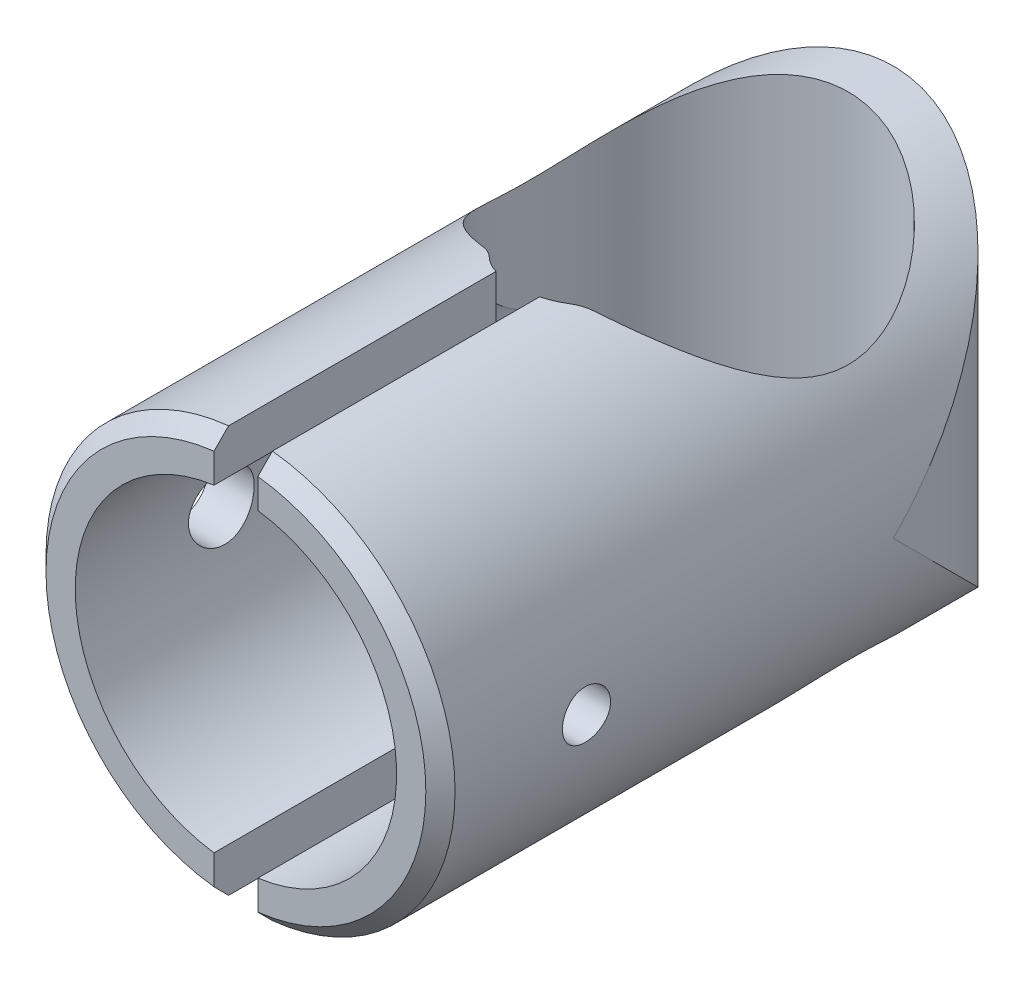
SolidWorks part; units mm, degrees
material "Сплав 2024"
ref_plane "Спереди" through (0, 0, 0) normal (0, 0, 1) x (1, 0, 0)
ref_plane "Сверху" through (0, 0, 0) normal (0, 1, 0) x (1, 0, 0)
ref_plane "Справа" through (0, 0, 0) normal (1, 0, 0) x (0, 0, -1)
sketch "Эскиз1" plane through (0, 0, 0) normal (0, 0, 1) x (1, 0, 0)
  circle A0 centre (0, 0) radius 14
  dimension "D1" = 28
extrude "Бобышка-Вытянуть1" add sketch "Эскиз1" along normal blind 45
ref_plane "Плоскость1" through (0, 14, 0) normal (0, 1, 0) x (1, 0, 0)
sketch "Эскиз2" plane through (0, 14, 0) normal (0, 1, 0) x (1, 0, 0)
  line L0 (0, 0) -> (0, -45) construction
  line L1 (-14, -45) -> (14, -45) construction
  line L2 (14, 0) -> (-14, 0) construction
  line L8 (-1.5, -24.8215) -> (-1.5, -45)
  line L9 (-1.5, -45) -> (1.5, -45)
  line L10 (1.5, -24.8215) -> (1.5, -45)
  line L11 (-1.5, -24.8215) -> (1.5, -45) construction
  line L12 (-1.5, -45) -> (1.5, -24.8215) construction
  arc A0 (1.5, -24.8215) -> (-1.5, -24.8215) centre (0, -14) ccw
  point P9 (0, -12.5)
  point P10 (0, -34.9108)
  point P17 (12.5, -12.5)
  dimension "D1" = 21.85
  dimension "D3" = 3
  dimension "D2" = 14
extrude "Вырез-Вытянуть1" cut sketch "Эскиз2" against normal through all
sketch "Эскиз3" plane through (0, 14, 0) normal (0, 1, 0) x (1, 0, 0)
  line L0 (14, -45) -> (14, 0) construction
  line L1 (14, 0) -> (-14, 0) construction
  line L2 (0, 0) -> (14, 0)
  line L3 (14, 0) -> (14, -14)
  arc A0 (14, -14) -> (0, 0) centre (0, -14) ccw
extrude "Вырез-Вытянуть2" cut sketch "Эскиз3" against normal through all
mirror "Зеркальное отражение1" about plane through (0, 0, 0) normal (1, 0, 0) of "Вырез-Вытянуть2"
sketch "Эскиз5" plane through (0, 0, 45) normal (0, 0, 1) x (1, 0, 0)
  circle A0 centre (0, 0) radius 11
  dimension "D1" = 22
extrude "Вырез-Вытянуть3" cut sketch "Эскиз5" against normal blind 31
ref_plane "Плоскость2" through (-14, 0, 0) normal (-1, 0, 0) x (0, 0, 1)
sketch "Эскиз7" plane through (-14, 0, 0) normal (-1, 0, 0) x (0, 0, 1)
  line L0 (45, 0) -> (0, 0) construction
  line L1 (45, -13.9194) -> (45, 13.9194) construction
  line L2 (35, 13.9194) -> (35, -13.9194) construction
  line L3 (45, 13.9194) -> (24.8215, 13.9194) construction
  line L4 (24.8215, -13.9194) -> (45, -13.9194) construction
  dimension "D1" = 10
hole_wizard "Отверстие с зазором M41" positions "Эскиз9" profile "Эскиз8" hole size "M4" standard "Ansi Metric"
sketch "Эскиз9" plane through (-14, 0, 0) normal (-1, 0, 0) x (0, 0, 1)
  line L0 (45, 0) -> (0, 0) construction
  line L1 (35, 13.9194) -> (35, -13.9194) construction
  point P0 (35, 0)
sketch "Эскиз8" plane through (-14, 0, 35) normal (0, 1, 0) x (0, 0, 1)
  line L0 (0, 0) -> (0, 6.3519)
  line L1 (0, 6.3519) -> (2.25, 5)
  line L2 (2.25, 5) -> (2.25, 0)
  line L5 (2.25, 0) -> (0, 0)
  line L10 (0, 6.3519) -> (-2.25, 5) construction
  line L11 (0, -6.35) -> (0, 107.95) construction
  dimension "Диаметр отверстия" = 4.5
  dimension "Глубина отверстия" = 5
  dimension "Угол заточки сверла" = 118
sketch "Эскиз10" plane through (0, 14, 0) normal (0, 1, 0) x (1, 0, 0)
  line L0 (0, 0) -> (0, -50) construction
  circle A0 centre (0, -22) radius 4
  arc A1 (14, -14) -> (-14, -14) centre (0, -14) ccw construction
  arc A2 (1.5, -24.8215) -> (-1.5, -24.8215) centre (0, -14) ccw construction
  dimension "D1" = 8
  dimension "D2" = 8
extrude "Вырез-Вытянуть5" cut sketch "Эскиз10" against normal through all
fillet "Скругление2" radius 3 4 edges at (3.1543, 12.089, 24.4597) (-3.1543, -12.089, 24.4597) (3.1543, -12.089, 24.4597) (-3.1543, 12.089, 24.4597)
ref_plane "Плоскость3" through (14, 0, 0) normal (1, 0, 0) x (0, 0, -1)
hole_wizard "Отверстие обработанное метчиком M4x0.71" positions "Эскиз12" profile "Эскиз11" tap size "M4x0.7" standard "Ansi Metric"
sketch "Эскиз12" plane through (14, 0, 0) normal (1, 0, 0) x (0, 0, -1)
  line L0 (-45, 0) -> (0, 0) construction
  line L1 (-35, 13.9194) -> (-35, -13.9194) construction
  point P0 (-35, 0)
sketch "Эскиз11" plane through (14, 0, 35) normal (0, 1, 0) x (0, 0, -1)
  line L0 (0, 0) -> (0, 12.4914)
  line L1 (0, 12.4914) -> (1.65, 11.5)
  line L2 (1.65, 11.5) -> (1.65, 0)
  line L5 (1.65, 0) -> (0, 0)
  line L10 (0, 12.4914) -> (-1.65, 11.5) construction
  line L11 (0, -6.35) -> (0, 107.95) construction
  dimension "Диаметр сверла" = 3.3
  dimension "Глубина сверла" = 11.5
  dimension "Угол заточки сверла" = 118
cosmetic thread "Отверстие резьбы1" parameters "D1"=3.1245, "D2"=4
chamfer "Фаска1" distance 1 angle 45 2 edges at (14, 0, 45) (-14, 0, 45)
